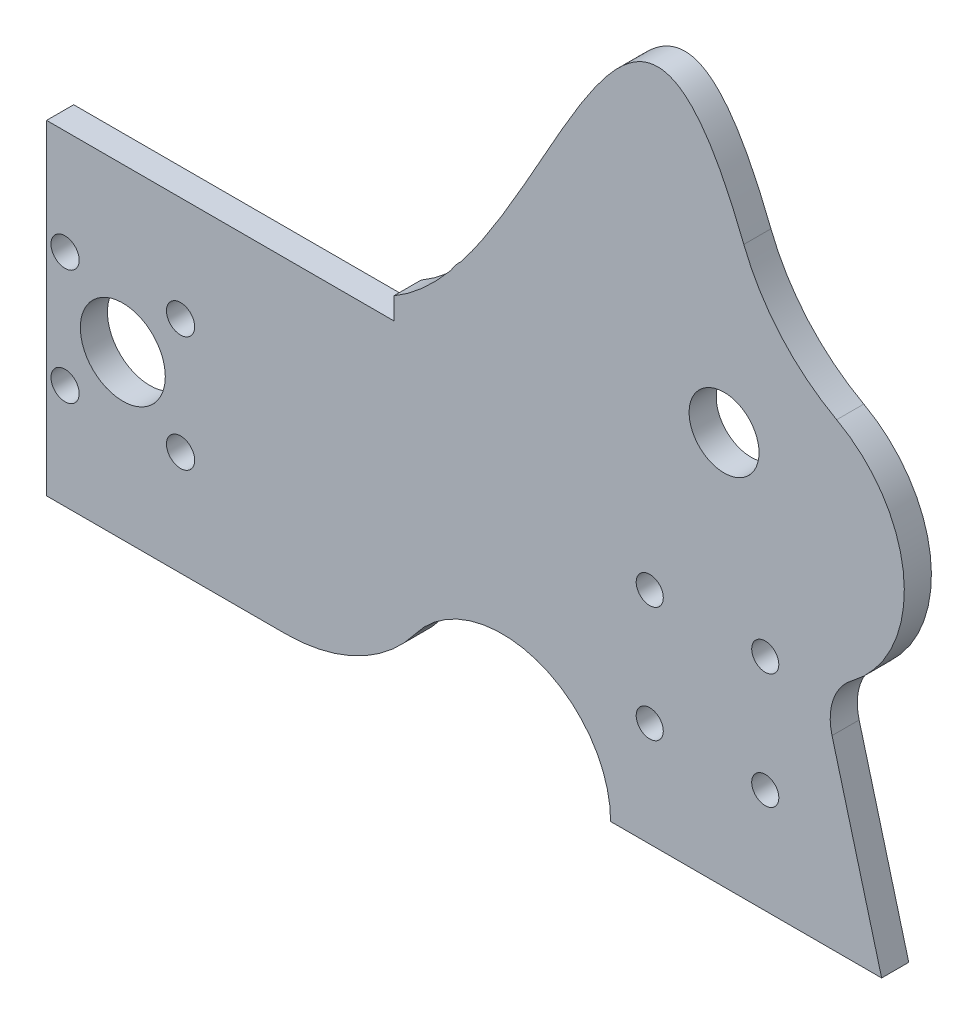
SolidWorks part; units mm, degrees
ref_plane "Front Plane" through (0, 0, 0) normal (0, 0, 1) x (1, 0, 0)
ref_plane "Top Plane" through (0, 0, 0) normal (0, 1, 0) x (1, 0, 0)
ref_plane "Right Plane" through (0, 0, 0) normal (1, 0, 0) x (0, 0, -1)
sketch "Sketch1" plane through (0, 0, 0) normal (0, 0, 1) x (1, 0, 0)
  line L0 (0, 0) -> (107.95, 0)
  line L3 (0, 38.1) -> (0, 25.4)
  line L4 (95.3675, 55.88) -> (0, 38.1)
  line L5 (0, 19.05) -> (100.2273, 19.05) construction
  line L6 (19.05, 19.05) -> (19.05, 28.62) construction
  line L7 (19.05, 19.05) -> (25.817, 25.817) construction
  line L8 (107.95, 0) -> (100.9363, 26.1756)
  line L10 (0, 12.7) -> (0, 0)
  line L11 (0, 25.4) -> (-7.62, 25.4)
  line L13 (0, 12.7) -> (-7.62, 12.7)
  line L14 (-7.62, 25.4) -> (-7.62, 12.7)
  line L15 (100.9363, 26.1756) -> (100.8688, 26.4276)
  arc A0 (100.8688, 26.4276) -> (95.3675, 55.88) centre (95.3675, 40.64) ccw
  circle A1 centre (95.3675, 40.64) radius 4.0957 construction
  circle A2 centre (19.05, 19.05) radius 9.57 construction
  circle A3 centre (25.817, 25.817) radius 1.651
  circle A4 centre (25.817, 12.283) radius 1.651
  circle A5 centre (12.283, 12.283) radius 1.651
  circle A6 centre (12.283, 25.817) radius 1.651
  point P26 (19.05, 19.05)
  dimension "D1" = 8.1915
  dimension "D5" = 15.24
  dimension "D4" = 19.14
  dimension "D7" = 3.302
  dimension "D11" = 97.0107
  dimension "D2" = 38.1
  dimension "D3" = 40.64
  dimension "D6" = 107.95
  dimension "D8" = 45
  dimension "D9" = 4
  dimension "D10" = 19.05
  dimension "D12" = 75
  dimension "D14" = 12.7
  dimension "D15" = 12.7
  dimension "D16" = 7.62
extrude "Boss-Extrude1" add sketch "Sketch1" along normal blind 3.175
sketch "Sketch2" plane through (0, 0, 3.175) normal (0, 0, 1) x (1, 0, 0)
  circle A0 centre (95.3675, 40.64) radius 38.1 construction
sketch "Sketch6" plane through (0, 0, 3.175) normal (0, 0, 1) x (1, 0, 0)
  line L0 (0, 0) -> (107.95, 0) construction
  line L1 (50.8, 0) -> (76.2, 0)
  arc A0 (76.2, 0) -> (50.8, 0) centre (63.5, 0) ccw
  dimension "D1" = 25.4
  dimension "D2" = 31.75
extrude "Cut-Extrude2" cut sketch "Sketch6" against normal blind 6.35
sketch "Sketch7" plane through (0, 0, 3.175) normal (0, 0, 1) x (1, 0, 0)
  line L0 (12.283, 25.817) -> (25.817, 12.283) construction
  line L1 (12.283, 12.283) -> (25.817, 25.817) construction
  circle A0 centre (19.05, 19.05) radius 4.9784
  circle A2 centre (80.7829, 12.2536) radius 1.5875
  circle A3 centre (94.316, 12.2536) radius 1.5875
  circle A4 centre (80.7829, 25.7876) radius 1.5875
  circle A5 centre (94.316, 25.7876) radius 1.5875
  dimension "D1" = 9.9568
extrude "Cut-Extrude3" cut sketch "Sketch7" against normal through all
fillet "Fillet1" radius 6.35 1 edges at (100.8688, 26.4276, 1.5875)
sketch "Sketch8" plane through (0, 0, 3.175) normal (0, 0, 1) x (1, 0, 0)
  line L1 (0, 38.1) -> (50.8, 38.1)
  line L2 (0, 38.1) -> (0, 50.8)
  line L3 (0, 50.8) -> (50.8, 50.8)
  line L4 (50.8, 38.1) -> (50.8, 50.8)
  dimension "D1" = 50.8
  dimension "D2" = 12.7
extrude "Cut-Extrude4" cut sketch "Sketch8" against normal blind 50.8
sketch "Sketch9" plane through (0, 0, 3.175) normal (0, 0, 1) x (1, 0, 0)
  line L3 (50.8, 40.64) -> (57.15, 40.64)
  line L5 (57.15, 40.64) -> (50.8, 40.64)
  line L6 (57.15, 40.64) -> (57.15, 50.8)
  line L7 (57.15, 50.8) -> (50.8, 50.8)
  line L8 (50.8, 40.64) -> (50.8, 50.8)
  line L9 (0, 38.1) -> (50.8, 38.1) construction
  line M8 (50.8, 47.571) -> (50.8, 38.1)
  line M21 (95.3675, 55.88) -> (50.8, 47.571)
  dimension "D1" = 10.16
  dimension "D2" = 2.54
  dimension "D3" = 6.35
extrude "Cut-Extrude5" cut sketch "Sketch9" against normal blind 19.304 contours L3 L6 M21 M8 region at (54.0583, 44.4092, 3.175)
fillet "Fillet6" radius 6.35 1 edges at (57.15, 40.64, 1.5875)
fillet "Fillet7" radius 6.35 1 edges at (57.15, 48.7549, 1.5875)
fillet "Fillet8" radius 19.05 1 edges at (50.8, 0, 1.5875)
sketch "Sketch12" plane through (0, 0, 3.175) normal (0, 0, 1) x (1, 0, 0)
  line L0 (107.95, 0) -> (146.812, 0) construction
  line L1 (8.0257, 45.4128) -> (80.6683, 75.7903) construction
  line L2 (95.3675, 40.64) -> (80.6683, 75.7903) construction
  line L3 (80.6683, 75.7903) -> (79.4434, 78.7195) construction
  line L4 (50.8, 40.64) -> (85.0271, 40.64)
  line L5 (85.0271, 40.64) -> (95.3675, 55.88)
  arc A0 (61.8128, 49.6242) -> (56.8883, 45.1859) centre (62.9766, 43.3817) ccw construction
  circle A1 centre (19.05, 19.05) radius 28.575 construction
  circle A2 centre (95.3675, 40.64) radius 38.1 construction
  circle A3 centre (80.6683, 75.7903) radius 3.175 construction
  spline S0 degree 3 poles (50.8, 40.64) (70.7778, 52.1788) (78.5943, 111.5434) (95.3675, 55.88) knots 0 0 0 0 1 1 1 1
  dimension "D2" = 6.35
  dimension "D1" = 38.862
extrude "Boss-Extrude2" add sketch "Sketch12" against normal blind 3.175
fillet "Fillet9" radius 24.13 1 edges at (95.3675, 55.88, 1.5875)
sketch "Sketch13" plane through (0, 38.1, 0) normal (0, 1, 0) x (1, 0, 0)
  line L0 (10.12, -3.175) -> (10.12, 0)
  line L1 (0, -3.175) -> (50.8, -3.175) construction
  line L2 (0, 0) -> (50.8, 0) construction
extrude "Cut-Extrude6" cut sketch "Sketch13" against normal through all
sketch "Sketch14" plane through (0, 0, 3.175) normal (0, 0, 1) x (1, 0, 0)
  circle A0 centre (89.49, 46.1076) radius 4.0958
  circle A1 centre (94.316, 25.7876) radius 1.5875 construction
  circle A2 centre (95.3675, 40.64) radius 4.0957 construction
  point P3 (95.3675, 40.64)
  point P4 (0, 0)
  point P5 (88.0877, 42.526)
  dimension "D1" = 4.826
  dimension "D2" = 20.32
extrude "Cut-Extrude7" cut sketch "Sketch14" against normal through all
